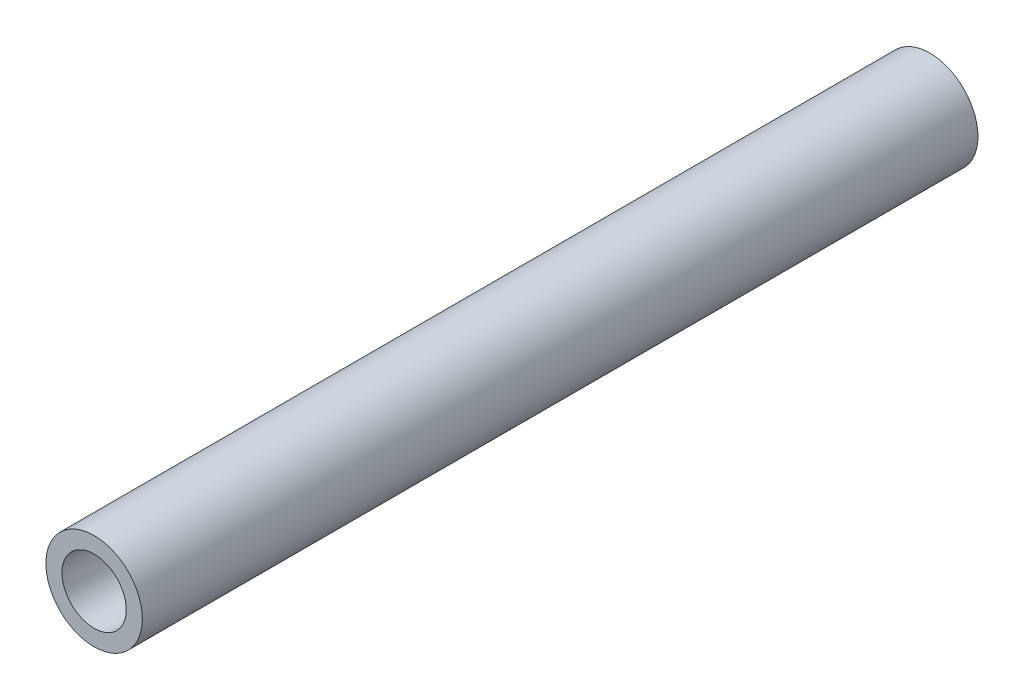
SolidWorks part; units mm, degrees
ref_plane "Front Plane" through (0, 0, 0) normal (0, 0, 1) x (1, 0, 0)
ref_plane "Top Plane" through (0, 0, 0) normal (0, 1, 0) x (1, 0, 0)
ref_plane "Right Plane" through (0, 0, 0) normal (1, 0, 0) x (0, 0, -1)
sketch "Sketch1" plane through (0, 0, 0) normal (0, 0, 1) x (1, 0, 0)
  circle A0 centre (0, 0) radius 7.5
  circle A1 centre (0, 0) radius 5
extrude "Boss-Extrude1" add sketch "Sketch1" along normal blind 65 and the other way blind 65
